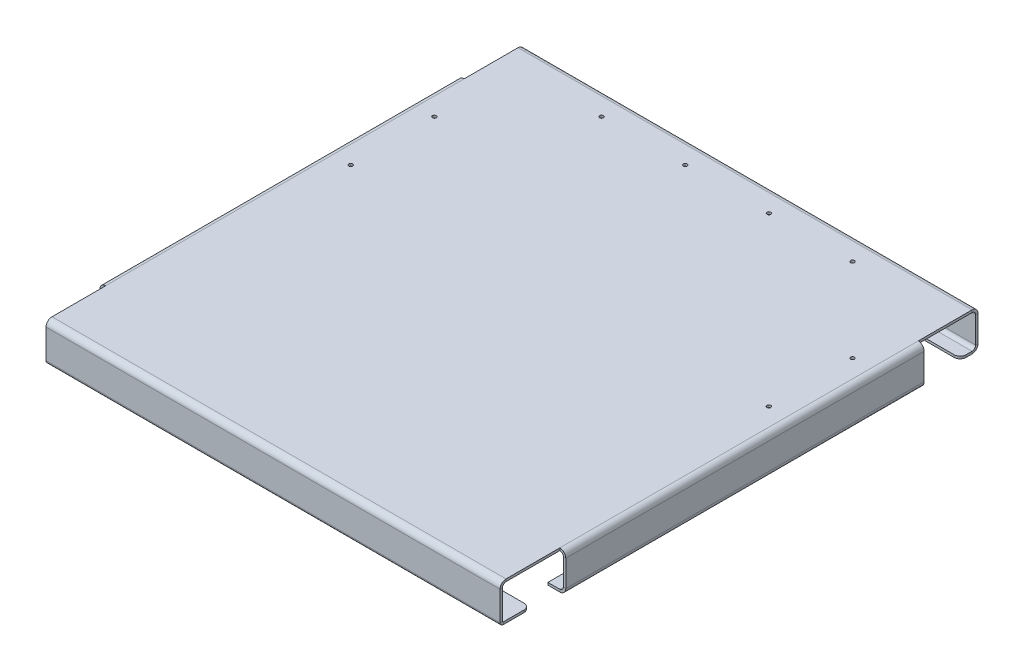
SolidWorks part; units mm, degrees
note: The reader was unsure of these and kept them because the rebuilt part matched: thickness of "Base-Flange1", "Edge-Flange3", "Edge-Flange11", "Edge-Flange12", "Edge-Flange13", "Edge-Flange14", "Edge-Flange15", "Edge-Flange16", "Edge-Flange17", "Sheet-Metal1", "Sheet-Metal5", "Sheet-Metal26", "Sheet-Metal30", "Sheet-Metal31", "Sheet-Metal33", "Sheet-Metal34", "Sheet-Metal35", "Sheet-Metal36", "Sheet-Metal37"; flange length of "Edge-Flange3", "Edge-Flange11", "Edge-Flange12", "Edge-Flange13", "Edge-Flange14", "Edge-Flange15", "Edge-Flange16", "Edge-Flange17".
ref_plane "Front Plane" through (0, 0, 0) normal (0, 0, 1) x (1, 0, 0)
ref_plane "Top Plane" through (0, 0, 0) normal (0, 1, 0) x (1, 0, 0)
ref_plane "Right Plane" through (0, 0, 0) normal (1, 0, 0) x (0, 0, -1)
sketch "Sketch1" plane through (0, 0, 0) normal (0, 1, 0) x (1, 0, 0)
  line L1 (190, -195) -> (-190, -195)
  line L2 (190, -195) -> (190, 195)
  line L3 (190, 195) -> (-190, 195)
  line L4 (-190, -195) -> (-190, 195)
  line L5 (190, -195) -> (-190, 195) construction
  line L6 (190, 195) -> (-190, -195) construction
  point P0 (0, 0)
  dimension "D1" = 380
  dimension "D2" = 390
base flange "Base-Flange1" sketch "Sketch1" thickness 2 reverse thickness direction no parameters "D1"=0.7366
edge flange "Edge-Flange3" sketch "Sketch15" flange angle 90 flange length 30 flange position bend outside bend radius 3 thickness 2 relief rectangular parameters "D6"=10
sketch "Sketch15" plane through (0, -2, -195) normal (0, 0, 1) x (-1, 0, 0)
  line L0 (190, 0) -> (-190, 0) construction
  line L2 (-190, 0) -> (-190, 28)
  line L3 (-190, 28) -> (190, 28)
  line L4 (190, 28) -> (190, 0)
  line L5 (190, 0) -> (-190, 0)
bend "EdgeBend3" bend radius 3 bend angle 90 parameters "D5"=3
edge flange "Edge-Flange11" sketch "Sketch72" flange angle 90 flange length 30 flange position bend outside bend radius 3 thickness 2 relief rectangular parameters "D6"=10
sketch "Sketch72" plane through (0, -2, 195) normal (0, 0, 1) x (-1, 0, 0)
  line L0 (190, 0) -> (-190, 0) construction
  line L2 (-190, 0) -> (-190, 28)
  line L3 (-190, 28) -> (190, 28)
  line L4 (190, 28) -> (190, 0)
  line L7 (190, 0) -> (-190, 0)
bend "EdgeBend11" bend radius 3 bend angle 90 parameters "D5"=8
edge flange "Edge-Flange12" sketch "Sketch81" flange angle 90 flange length 15 flange position material outside bend radius 3 thickness 2 relief rectangular parameters "D6"=10
sketch "Sketch81" plane through (0, -30, -198) normal (0, -1, 0) x (1, 0, 0)
  line L2 (-190, 0) -> (-190, 13)
  line L3 (-190, 13) -> (190, 13)
  line L4 (190, 13) -> (190, 0)
  line L15 (-190, 0) -> (190, 0) construction
  line L16 (-190, 0) -> (190, 0)
bend "EdgeBend12" bend radius 3 bend angle 90 parameters "D5"=9
edge flange "Edge-Flange13" sketch "Sketch84" flange angle 90 flange length 25 flange position material outside bend radius 0.7366 thickness 2 relief rectangular parameters "D6"=10
sketch "Sketch84" plane through (0, -30, 198) normal (0, 1, 0) x (1, 0, 0)
  line L2 (-190, 0) -> (-190, 23)
  line L3 (-190, 23) -> (190, 23)
  line L4 (190, 23) -> (190, 0)
  line L5 (190, 0) -> (-190, 0) construction
  line L6 (190, 0) -> (-190, 0)
bend "EdgeBend13" bend radius 0.7366 bend angle 90 parameters "D5"=10
hole_wizard "Ø1.0mm Dowel Hole2" positions "Sketch86" profile "Sketch87" hole size "Ø1.0" standard "ANSI Metric" end condition up to next
sketch "Sketch86" plane through (0, 0, 0) normal (0, 1, 0) x (1, 0, 0)
  line L0 (190, 195) -> (-190, 195) construction
  line L1 (-190, 200) -> (190, 200) construction
  point P0 (-175, 40)
  point P4 (-175, 110)
  point P8 (-105, 180)
  point P10 (-35, 180)
  point P12 (35, 180)
  point P16 (175, 110)
  point P20 (175, 40)
  point P35 (105, 180)
  point P45 (0, 195)
  dimension "D4" = 70
  dimension "D1" = 70
  dimension "D2" = 70
  dimension "D3" = 70
  dimension "D5" = 70
  dimension "D6" = 70
  dimension "D7" = 70
  dimension "D8" = 35
  dimension "D9" = 20
sketch "Sketch87" plane through (-175, 0, -40) normal (1, 0, 0) x (0, 0, 1)
  line L0 (0, 0) -> (0, 2)
  line L1 (0, 2) -> (1.6, 2)
  line L2 (1.6, 2) -> (1.6, 0)
  line L5 (1.6, 0) -> (0, 0)
  line L11 (0, -6.35) -> (0, 107.95) construction
  dimension "Thru Hole Dia." = 3.2
  dimension "Thru Hole Depth" = 2
fillet "Fillet1" radius 5 4 edges at (190, -31, 175) (-190, -31, 175) (-190, -31, -185) (190, -31, -185)
edge flange "Edge-Flange14" sketch "Sketch91" flange angle 90 flange length 32 flange position bend outside bend radius 3 thickness 2 relief rectangular parameters "D6"=10
sketch "Sketch91" plane through (190, -2, 0) normal (1, 0, 0) x (0, 0, 1)
  line L0 (195, 0) -> (-195, 0) construction
  line L1 (150, 0) -> (-150, 0)
  line L2 (-150, 0) -> (-150, 30)
  line L3 (-150, 30) -> (150, 30)
  line L4 (150, 30) -> (150, 0)
  line L5 (200, 27.2634) -> (200, 3) construction
  line L6 (-200, 25) -> (-200, 3) construction
  dimension "D1" = 50
  dimension "D2" = 50
  dimension "D3" = 30
bend "EdgeBend14" bend radius 3 bend angle 90 parameters "D5"=11
edge flange "Edge-Flange15" sketch "Sketch94" flange angle 90 flange length 32 flange position bend outside bend radius 3 thickness 2 relief rectangular parameters "D6"=10
sketch "Sketch94" plane through (-190, -2, 0) normal (1, 0, 0) x (0, 0, 1)
  line L0 (-195, 0) -> (195, 0) construction
  line L2 (-150, 0) -> (-150, 30)
  line L3 (-150, 30) -> (150, 30)
  line L4 (150, 30) -> (150, 0)
  line L5 (195, 0) -> (-195, 0) construction
  line L6 (150, 0) -> (-150, 0)
  line L7 (200, 3) -> (200, 27.2634) construction
  line L8 (-200, 3) -> (-200, 25) construction
  dimension "D1" = 50
  dimension "D2" = 50
  dimension "D3" = 30
bend "EdgeBend15" bend radius 3 bend angle 90 parameters "D5"=12
edge flange "Edge-Flange16" sketch "Sketch97" flange angle 90 flange length 15 flange position material inside bend radius 3 thickness 2 relief rectangular parameters "D6"=10
sketch "Sketch97" plane through (193, -32, 0) normal (0, 1, 0) x (0, 0, -1)
  line L2 (-150, 0) -> (-150, 13)
  line L3 (-150, 13) -> (150, 13)
  line L4 (150, 13) -> (150, 0)
  line L5 (150, 0) -> (-150, 0) construction
  line L6 (150, 0) -> (-150, 0)
bend "EdgeBend16" bend radius 3 bend angle 90 parameters "D5"=13
edge flange "Edge-Flange17" sketch "Sketch100" flange angle 90 flange length 15 flange position material inside bend radius 3 thickness 2 relief rectangular parameters "D6"=10
sketch "Sketch100" plane through (-193, -32, 0) normal (0, 1, 0) x (0, 0, 1)
  line L2 (-150, 0) -> (-150, 13)
  line L3 (-150, 13) -> (150, 13)
  line L4 (150, 13) -> (150, 0)
  line L9 (150, 0) -> (-150, 0) construction
  line L10 (150, 0) -> (-150, 0)
bend "EdgeBend17" bend radius 3 bend angle 90 parameters "D5"=14
sketch "Bend-Lines1" [suppressed] plane through (0, 0, 0) normal (0, 1, 0) x (1, 0, 0)
sketch "Bounding-Box1" [suppressed] plane through (0, 0, 0) normal (0, 1, 0) x (1, 0, 0)
fillet "Fillet2" [suppressed] radius 3
sheet metal parameters "Sheet-Metal1" thickness 2 parameters "D1"=0.7366, "D7"=3
flat pattern "Flat-Pattern1" [suppressed]
sketch "Bend-Lines2" plane through (0, 0, 0) normal (0, 1, 0) x (1, 0, 0)
sketch3d "Bounding-Box2" [suppressed]
  line L0 (-175, -150, 0) -> (175, -150, 0) construction
  line L1 (-175, 150, 0) -> (175, 150, 0) construction
  line L2 (-175, -150, 0) -> (-175, 150, 0) construction
  line L3 (175, -150, 0) -> (175, 150, 0) construction
sheet metal parameters "Sheet-Metal5" thickness 2 parameters "D1"=0.7366, "D7"=3
flat pattern "Flat-Pattern1"
sketch "Bend-Lines2" plane through (0, 0, 0) normal (0, 1, 0) x (1, 0, 0)
  line L0 (-172.1051, 154.9293) -> (-172.1051, -150) construction
  line L1 (-172.1051, 154.9293) -> (-172.1051, -150) construction
  line L2 (172.1051, -150) -> (172.1051, 154.9293) construction
  line L3 (172.1051, -150) -> (172.1051, 154.9293) construction
  line L4 (171.9293, 155.1051) -> (-171.9293, 155.1051) construction
  line L5 (171.9293, 155.1051) -> (-171.9293, 155.1051) construction
sketch3d "Bounding-Box2" [suppressed]
  line L0 (219.2102, 202.2102, 0) -> (-219.2102, 202.2102, 0) construction
  line L1 (219.2102, -150, 0) -> (-219.2102, -150, 0) construction
  line L2 (219.2102, 202.2102, 0) -> (219.2102, -150, 0) construction
  line L3 (-219.2102, 202.2102, 0) -> (-219.2102, -150, 0) construction
bend of the flat pattern "Flatten-<EdgeBend3>1"
sheet metal parameters "Sheet-Metal26" thickness 2 parameters "D1"=0.7366, "D7"=3
flat pattern "Flat-Pattern1"
sketch "Bend-Lines2" plane through (0, 0, 0) normal (0, 1, 0) x (1, 0, 0)
  line L0 (-185.5343, 177.9293) -> (-185.5343, -177.9293) construction
  line L1 (-185.5343, 177.9293) -> (-185.5343, -177.9293) construction
  line L2 (185.5343, -177.9293) -> (185.5343, 177.9293) construction
  line L3 (185.5343, -177.9293) -> (185.5343, 177.9293) construction
  line L4 (184.9293, 178.5343) -> (-184.9293, 178.5343) construction
  line L5 (184.9293, 178.5343) -> (-184.9293, 178.5343) construction
  line L6 (282.2051, 0.3746) -> (346.3897, 176.7205) construction
  line L7 (282.2051, 0.3746) -> (346.3897, 176.7205) construction
  line L8 (-346.3897, 176.7205) -> (-282.2051, 0.3746) construction
  line L9 (-346.3897, 176.7205) -> (-282.2051, 0.3746) construction
  line L10 (213.0686, -0.0343) -> (281.6211, -0.0343) construction
  line L11 (213.0686, -0.0343) -> (281.6211, -0.0343) construction
  line L12 (-281.6211, -0.0343) -> (-213.0686, -0.0343) construction
  line L13 (-281.6211, -0.0343) -> (-213.0686, -0.0343) construction
  line L14 (-184.9293, -178.5343) -> (184.9293, -178.5343) construction
  line L15 (-184.9293, -178.5343) -> (184.9293, -178.5343) construction
sketch3d "Bounding-Box2" [suppressed]
  line L0 (-367.5651, -204.0685, 0) -> (367.565, -204.0686, 0) construction
  line L1 (-367.565, 346.0687, 0) -> (367.5651, 346.0686, 0) construction
  line L2 (-367.5651, -204.0685, 0) -> (-367.565, 346.0687, 0) construction
  line L3 (367.565, -204.0686, 0) -> (367.5651, 346.0686, 0) construction
bend of the flat pattern "Flatten-<EdgeBend3>1"
bend of the flat pattern "Flatten-<EdgeBend11>1"
sheet metal parameters "Sheet-Metal30" thickness 2 parameters "D1"=0.7366, "D7"=3
flat pattern "Flat-Pattern1"
sketch "Bend-Lines2" plane through (0, 0, 0) normal (0, 1, 0) x (1, 0, 0)
  line L0 (188, 206.4248) -> (-188, 206.4248) construction
  line L1 (188, 206.4248) -> (-188, 206.4248) construction
  line L4 (188, 178.1416) -> (-188, 178.1416) construction
  line L5 (188, 178.1416) -> (-188, 178.1416) construction
  line L14 (-188, -178.1416) -> (188, -178.1416) construction
  line L15 (-188, -178.1416) -> (188, -178.1416) construction
sketch3d "Bounding-Box2" [suppressed]
  line L0 (-188, 229.5664, 0) -> (-188, -206.2832, 0) construction
  line L1 (188, 229.5664, 0) -> (188, -206.2832, 0) construction
  line L2 (-188, 229.5664, 0) -> (188, 229.5664, 0) construction
  line L3 (-188, -206.2832, 0) -> (188, -206.2832, 0) construction
bend of the flat pattern "Flatten-<EdgeBend3>1"
bend of the flat pattern "Flatten-<EdgeBend11>1"
bend of the flat pattern "Flatten-<EdgeBend12>1"
sheet metal parameters "Sheet-Metal31" thickness 2 parameters "D1"=0.7366, "D7"=3
flat pattern "Flat-Pattern1"
sketch "Bend-Lines2" plane through (0, 0, 0) normal (0, 1, 0) x (1, 0, 0)
  line L0 (188, 206.4248) -> (-188, 206.4248) construction
  line L1 (188, 206.4248) -> (-188, 206.4248) construction
  line L2 (-188, -206.9105) -> (188, -206.9105) construction
  line L3 (-188, -206.9105) -> (188, -206.9105) construction
  line L4 (188, 178.1416) -> (-188, 178.1416) construction
  line L5 (188, 178.1416) -> (-188, 178.1416) construction
  line L14 (-188, -178.1416) -> (188, -178.1416) construction
  line L15 (-188, -178.1416) -> (188, -178.1416) construction
sketch3d "Bounding-Box2" [suppressed]
  line L0 (-188, 229.5664, 0) -> (-188, -230.5378, 0) construction
  line L1 (188, 229.5664, 0) -> (188, -230.5378, 0) construction
  line L2 (-188, 229.5664, 0) -> (188, 229.5664, 0) construction
  line L3 (-188, -230.5378, 0) -> (188, -230.5378, 0) construction
bend of the flat pattern "Flatten-<EdgeBend3>1"
bend of the flat pattern "Flatten-<EdgeBend11>1"
bend of the flat pattern "Flatten-<EdgeBend12>1"
bend of the flat pattern "Flatten-<EdgeBend13>1"
sheet metal parameters "Sheet-Metal33" thickness 2 parameters "D1"=0.7366, "D7"=3
flat pattern "Flat-Pattern1" [suppressed]
sketch "Bend-Lines2" plane through (0, 0, 0) normal (0, 1, 0) x (1, 0, 0)
  line L0 (190, 206.4248) -> (-190, 206.4248) construction
  line L1 (190, 206.4248) -> (-190, 206.4248) construction
  line L2 (-190, -206.9105) -> (190, -206.9105) construction
  line L3 (-190, -206.9105) -> (190, -206.9105) construction
  line L4 (190, 178.1416) -> (-190, 178.1416) construction
  line L5 (190, 178.1416) -> (-190, 178.1416) construction
  line L14 (-190, -178.1416) -> (190, -178.1416) construction
  line L15 (-190, -178.1416) -> (190, -178.1416) construction
sketch3d "Bounding-Box2" [suppressed]
  line L0 (190, 219.5663, 0) -> (190, -230.5378, 0) construction
  line L1 (-190, 219.5664, 0) -> (-190, -230.5378, 0) construction
  line L2 (190, 219.5663, 0) -> (-190, 219.5664, 0) construction
  line L3 (190, -230.5378, 0) -> (-190, -230.5378, 0) construction
bend of the flat pattern "Flatten-<EdgeBend3>1"
bend of the flat pattern "Flatten-<EdgeBend11>1"
bend of the flat pattern "Flatten-<EdgeBend12>1"
bend of the flat pattern "Flatten-<EdgeBend13>1"
sketch "Sketch85-1" plane through (0, 0, 176.2832) normal (0, 1, 0) x (1, 0, 0)
  line L1 (-112, -21.2634) -> (-162, -21.2634)
  line L3 (-112, -13.2634) -> (-162, -13.2634)
  line L5 (-112, -21.2634) -> (-162, -13.2634) construction
  line L6 (-112, -13.2634) -> (-162, -21.2634) construction
  line L7 (128, -21.2634) -> (78, -21.2634)
  line L9 (128, -13.2634) -> (78, -13.2634)
  line L11 (128, -21.2634) -> (78, -13.2634) construction
  line L12 (128, -13.2634) -> (78, -21.2634) construction
  line L13 (-190, -29.2634) -> (190, -29.2634) construction
  line L14 (-190, 390.8496) -> (-190, -49.2546) construction
  arc A0 (-162, -13.2634) -> (-162, -21.2634) centre (-162, -17.2634) ccw
  arc A1 (-112, -13.2634) -> (-112, -21.2634) centre (-112, -17.2634) cw
  arc A2 (128, -13.2634) -> (128, -21.2634) centre (128, -17.2634) cw
  arc A3 (78, -13.2634) -> (78, -21.2634) centre (78, -17.2634) ccw
  point P0 (-137, -17.2634)
  point P5 (103, -17.2634)
  dimension "D5" = 4
  dimension "D4" = 28
  dimension "D1" = 50
  dimension "D2" = 8
  dimension "D3" = 8
  dimension "D6" = 190
sheet metal parameters "Sheet-Metal34" thickness 2 parameters "D1"=0.7366, "D7"=3
flat pattern "Flat-Pattern1"
sketch "Bend-Lines2" plane through (0, 0, 0) normal (0, 1, 0) x (1, 0, 0)
  line L0 (190, 206.4248) -> (-190, 206.4248) construction
  line L1 (190, 206.4248) -> (-190, 206.4248) construction
  line L2 (-190, -206.9105) -> (190, -206.9105) construction
  line L3 (-190, -206.9105) -> (190, -206.9105) construction
  line L4 (190, 178.1416) -> (-190, 178.1416) construction
  line L5 (190, 178.1416) -> (-190, 178.1416) construction
  line L6 (193.1416, -175) -> (193.1416, 175) construction
  line L7 (193.1416, -175) -> (193.1416, 175) construction
  line L14 (-190, -178.1416) -> (190, -178.1416) construction
  line L15 (-190, -178.1416) -> (190, -178.1416) construction
sketch3d "Bounding-Box2" [suppressed]
  line L0 (223.2832, 219.5663, 0) -> (223.2832, -230.5378, 0) construction
  line L1 (-190, 219.5664, 0) -> (-190, -230.5378, 0) construction
  line L2 (223.2832, 219.5663, 0) -> (-190, 219.5664, 0) construction
  line L3 (223.2832, -230.5378, 0) -> (-190, -230.5378, 0) construction
bend of the flat pattern "Flatten-<EdgeBend3>1"
bend of the flat pattern "Flatten-<EdgeBend11>1"
bend of the flat pattern "Flatten-<EdgeBend12>1"
bend of the flat pattern "Flatten-<EdgeBend13>1"
bend of the flat pattern "Flatten-<EdgeBend14>1"
sheet metal parameters "Sheet-Metal35" thickness 2 parameters "D1"=0.7366, "D7"=3
flat pattern "Flat-Pattern1"
sketch "Bend-Lines2" plane through (0, 0, 0) normal (0, 1, 0) x (1, 0, 0)
  line L0 (190, 206.4248) -> (-190, 206.4248) construction
  line L1 (190, 206.4248) -> (-190, 206.4248) construction
  line L2 (-190, -206.9105) -> (190, -206.9105) construction
  line L3 (-190, -206.9105) -> (190, -206.9105) construction
  line L4 (190, 178.1416) -> (-190, 178.1416) construction
  line L5 (190, 178.1416) -> (-190, 178.1416) construction
  line L6 (193.1416, -60) -> (193.1416, 60) construction
  line L7 (193.1416, -60) -> (193.1416, 60) construction
  line L8 (-193.1416, 60) -> (-193.1416, -60) construction
  line L9 (-193.1416, 60) -> (-193.1416, -60) construction
  line L14 (-190, -178.1416) -> (190, -178.1416) construction
  line L15 (-190, -178.1416) -> (190, -178.1416) construction
sketch3d "Bounding-Box2" [suppressed]
  line L0 (223.2832, 219.5663, 0) -> (223.2832, -230.5378, 0) construction
  line L1 (-223.2832, 219.5664, 0) -> (-223.2832, -230.5378, 0) construction
  line L2 (223.2832, 219.5663, 0) -> (-223.2832, 219.5664, 0) construction
  line L3 (223.2832, -230.5378, 0) -> (-223.2832, -230.5378, 0) construction
bend of the flat pattern "Flatten-<EdgeBend3>1"
bend of the flat pattern "Flatten-<EdgeBend11>1"
bend of the flat pattern "Flatten-<EdgeBend12>1"
bend of the flat pattern "Flatten-<EdgeBend13>1"
bend of the flat pattern "Flatten-<EdgeBend14>1"
bend of the flat pattern "Flatten-<EdgeBend15>1"
sheet metal parameters "Sheet-Metal36" thickness 2 parameters "D1"=0.7366, "D7"=3
flat pattern "Flat-Pattern1"
sketch "Bend-Lines2" plane through (0, 0, 0) normal (0, 1, 0) x (1, 0, 0)
  line L0 (190, 206.4248) -> (-190, 206.4248) construction
  line L1 (190, 206.4248) -> (-190, 206.4248) construction
  line L2 (-190, -206.9105) -> (190, -206.9105) construction
  line L3 (-190, -206.9105) -> (190, -206.9105) construction
  line L4 (190, 178.1416) -> (-190, 178.1416) construction
  line L5 (190, 178.1416) -> (-190, 178.1416) construction
  line L6 (193.1416, -60) -> (193.1416, 60) construction
  line L7 (193.1416, -60) -> (193.1416, 60) construction
  line L8 (-193.1416, 60) -> (-193.1416, -60) construction
  line L9 (-193.1416, 60) -> (-193.1416, -60) construction
  line L10 (221.4248, -60) -> (221.4248, 60) construction
  line L11 (221.4248, -60) -> (221.4248, 60) construction
  line L14 (-190, -178.1416) -> (190, -178.1416) construction
  line L15 (-190, -178.1416) -> (190, -178.1416) construction
sketch3d "Bounding-Box2" [suppressed]
  line L0 (-223.2832, -230.5378, 0) -> (234.5664, -230.5378, 0) construction
  line L1 (-223.2832, 219.5664, 0) -> (234.5664, 219.5663, 0) construction
  line L2 (-223.2832, -230.5378, 0) -> (-223.2832, 219.5664, 0) construction
  line L3 (234.5664, -230.5378, 0) -> (234.5664, 219.5663, 0) construction
bend of the flat pattern "Flatten-<EdgeBend3>1"
bend of the flat pattern "Flatten-<EdgeBend11>1"
bend of the flat pattern "Flatten-<EdgeBend12>1"
bend of the flat pattern "Flatten-<EdgeBend13>1"
bend of the flat pattern "Flatten-<EdgeBend14>1"
bend of the flat pattern "Flatten-<EdgeBend15>1"
bend of the flat pattern "Flatten-<EdgeBend16>1"
sheet metal parameters "Sheet-Metal37" thickness 2 parameters "D1"=0.7366, "D7"=3
flat pattern "Flat-Pattern1"
sketch "Bend-Lines2" [suppressed] plane through (0, 0, 0) normal (0, 1, 0) x (1, 0, 0)
  line L0 (190, 226.4248) -> (-190, 226.4248) construction
  line L1 (190, 226.4248) -> (-190, 226.4248) construction
  line L2 (-190, -226.9105) -> (190, -226.9105) construction
  line L3 (-190, -226.9105) -> (190, -226.9105) construction
  line L4 (190, 198.1416) -> (-190, 198.1416) construction
  line L5 (190, 198.1416) -> (-190, 198.1416) construction
  line L6 (193.1416, -150) -> (193.1416, 150) construction
  line L7 (193.1416, -150) -> (193.1416, 150) construction
  line L8 (-193.1416, 150) -> (-193.1416, -150) construction
  line L9 (-193.1416, 150) -> (-193.1416, -150) construction
  line L10 (221.4248, -150) -> (221.4248, 150) construction
  line L11 (221.4248, -150) -> (221.4248, 150) construction
  line L12 (-221.4248, 150) -> (-221.4248, -150) construction
  line L13 (-221.4248, 150) -> (-221.4248, -150) construction
  line L14 (-190, -198.1416) -> (190, -198.1416) construction
  line L15 (-190, -198.1416) -> (190, -198.1416) construction
sketch3d "Bounding-Box2" [suppressed]
  line L0 (234.5664, 239.5663, 0) -> (234.5664, -250.5378, 0) construction
  line L1 (-234.5663, 239.5664, 0) -> (-234.5664, -250.5378, 0) construction
  line L2 (234.5664, 239.5663, 0) -> (-234.5663, 239.5664, 0) construction
  line L3 (234.5664, -250.5378, 0) -> (-234.5664, -250.5378, 0) construction
bend of the flat pattern "Flatten-<EdgeBend3>1"
bend of the flat pattern "Flatten-<EdgeBend11>1"
bend of the flat pattern "Flatten-<EdgeBend12>1"
bend of the flat pattern "Flatten-<EdgeBend13>1"
bend of the flat pattern "Flatten-<EdgeBend14>1"
bend of the flat pattern "Flatten-<EdgeBend15>1"
bend of the flat pattern "Flatten-<EdgeBend16>1"
bend of the flat pattern "Flatten-<EdgeBend17>1"
